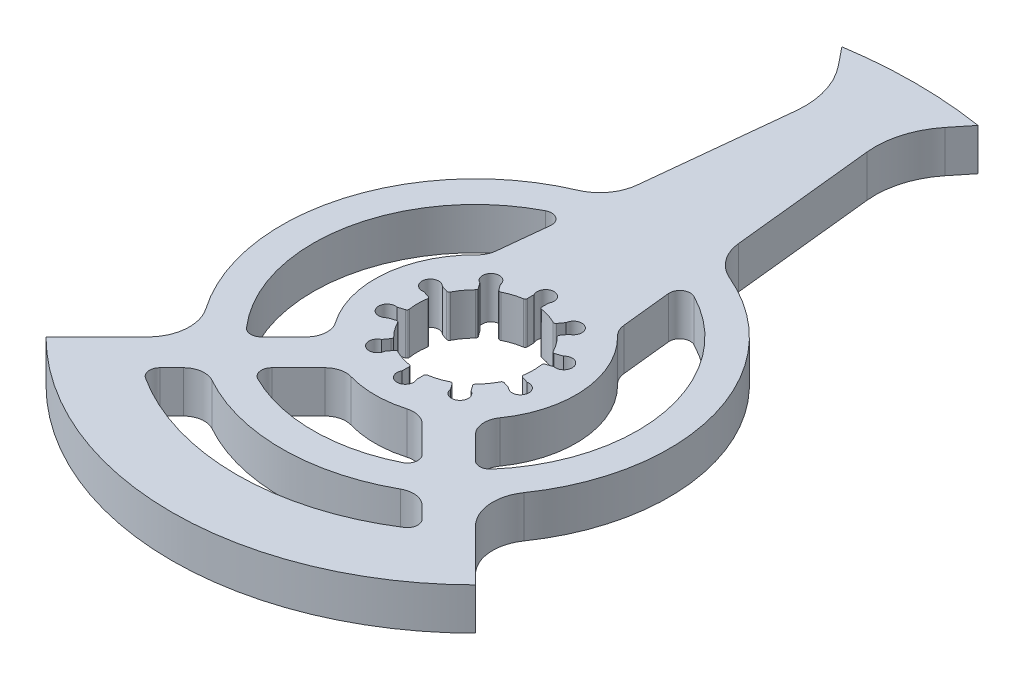
SolidWorks part; units mm, degrees
material "AISI Type A2 Tool Steel"
ref_plane "Front Plane" through (0, 0, 0) normal (0, 0, 1) x (1, 0, 0)
ref_plane "Top Plane" through (0, 0, 0) normal (0, 1, 0) x (1, 0, 0)
ref_plane "Right Plane" through (0, 0, 0) normal (1, 0, 0) x (0, 0, -1)
other "Center of Mass"
other "Bounding Box"
ref_plane "Default Plane" through (0, 2.286, 19.05) normal (0, -1, 0) x (-1, 0, 0)
sketch "Sketch1" plane through (0, 0, 0) normal (0, 1, 0) x (1, 0, 0)
  circle A0 centre (0, 0) radius 133.35 construction
  circle A1 centre (0, 0) radius 30.48
  circle A2 centre (0, 0) radius 17.4625
  dimension "D1" = 266.7
  dimension "D2" = 60.96
  dimension "D3" = 34.925
extrude "Boss-Extrude1" add sketch "Sketch1" along normal mid plane 12.7
sketch "Sketch2" plane through (0, 6.35, 0) normal (0, 1, 0) x (1, 0, 0)
  line L0 (-10.795, 107.95) -> (-19.6961, 23.2614)
  line L1 (19.6961, 23.2614) -> (10.795, 107.95)
  line L4 (0, 0) -> (0, 133.35) construction
  line L5 (-10.795, 107.95) -> (0, 107.95) construction
  line L6 (0, 107.95) -> (10.795, 107.95) construction
  line L7 (-20.6375, 131.7434) -> (0, 0) construction
  line L8 (-20.6375, 131.7434) -> (124.4119, -47.9991) construction
  line L9 (-20.6375, 131.7434) -> (-16.1956, 126.2391)
  line L10 (20.6375, 131.7434) -> (16.1956, 126.2391)
  circle A0 centre (0, 0) radius 133.35 construction
  circle A1 centre (0, 0) radius 133.35 construction
  arc A2 (-20.6375, 131.7434) -> (20.6375, 131.7434) centre (0, 0) cw
  circle A5 centre (0, 0) radius 30.48
  arc A6 (19.6961, 23.2614) -> (-19.6961, 23.2614) centre (0, 0) ccw
  arc A7 (-19.6961, 23.2614) -> (19.6961, 23.2614) centre (0, 0) ccw construction
  arc A9 (-16.1956, 126.2391) -> (-10.795, 107.95) centre (-35.6252, 110.5598) cw
  arc A10 (16.1956, 126.2391) -> (10.795, 107.95) centre (35.6252, 110.5598) ccw
  dimension "D3" = 41.275
  dimension "D4" = 25.4
  dimension "D5" = 6
  dimension "D6" = 10.795
  dimension "D1" = 30
  dimension "D2" = 0
extrude "Boss-Extrude2" add sketch "Sketch2" against normal through all
sketch "Sketch3" plane through (0, 6.35, 0) normal (0, 1, 0) x (1, 0, 0)
  line L0 (-65.1069, -65.1069) -> (-21.5526, -21.5526)
  line L1 (21.5526, -21.5526) -> (65.1069, -65.1069)
  line L2 (0, -30.48) -> (0, -92.075) construction
  line L4 (-21.5526, -21.5526) -> (0, 0) construction
  line L5 (0, 0) -> (21.5526, -21.5526) construction
  arc A0 (-65.1069, -65.1069) -> (65.1069, -65.1069) centre (0, 0) ccw
  circle A1 centre (0, 0) radius 30.48 construction
  arc A3 (-21.5526, -21.5526) -> (21.5526, -21.5526) centre (0, 0) ccw
  point P13 (0, -92.075)
  dimension "D2" = 92.075
  dimension "D1" = 90
extrude "Boss-Extrude3" add sketch "Sketch3" against normal through all
sketch "Sketch5" plane through (0, 6.35, 0) normal (0, 1, 0) x (1, 0, 0)
  line L0 (0, 17.4625) -> (0, 21.2725) construction
  line L2 (-2.2225, 17.3205) -> (2.2225, 17.3205)
  line L3 (-2.2225, 17.3205) -> (-2.2225, 20.0168)
  line L5 (2.2225, 17.3205) -> (2.2225, 20.0168)
  arc A0 (2.2225, 20.0168) -> (-2.2225, 20.0168) centre (0, 21.2725) ccw
  circle A1 centre (0, 0) radius 17.4625 construction
  circle A2 centre (0, 21.2725) radius 4.5847 construction
  dimension "D2" = 5.1054
  dimension "D4" = 9.1694
  dimension "D1" = 3.81
  dimension "D3" = 4.445
extrude "Cut-Extrude2" cut sketch "Sketch5" against normal through all
pattern_circular "CirPattern1" count 10 over 360 about axis through (0, 6.35, 0) along (0, -1, 0) of "Cut-Extrude2"
sketch "Sketch6" plane through (0, 6.35, 0) normal (0, 1, 0) x (1, 0, 0)
  circle A0 centre (0, 0) radius 17.526
  arc A1 (-11.9788, 12.7062) -> (-15.786, 7.466) centre (0, 0) ccw construction
  dimension "D1" = 0.0635
extrude "Cut-Extrude3" cut sketch "Sketch6" against normal through all
sketch "Sketch7" plane through (0, 6.35, 0) normal (0, 1, 0) x (1, 0, 0)
  line L0 (-42.454, -58.6185) -> (-11.8976, -28.062)
  line L1 (11.8976, -28.062) -> (42.454, -58.6185)
  line L3 (-21.5526, -21.5526) -> (-65.1069, -65.1069) construction
  line L4 (65.1069, -65.1069) -> (21.5526, -21.5526) construction
  line L5 (-42.454, -58.6185) -> (-50.5363, -50.5363) construction
  line L6 (42.454, -58.6185) -> (50.5363, -50.5363) construction
  arc A0 (-11.8976, -28.062) -> (11.8976, -28.062) centre (0, 0) ccw
  arc A1 (-42.454, -58.6185) -> (42.454, -58.6185) centre (0, 0) ccw
  arc A2 (-65.1069, -65.1069) -> (65.1069, -65.1069) centre (0, 0) ccw construction
  arc A4 (21.5526, -21.5526) -> (19.6961, 23.2614) centre (0, 0) ccw construction
  dimension "D1" = 19.6977
  dimension "D2" = 11.43
extrude "Cut-Extrude4" cut sketch "Sketch7" against normal through all
sketch "Sketch8" plane through (0, 6.35, 0) normal (0, 1, 0) x (1, 0, 0)
  circle A0 centre (0, 0) radius 49.2125
  circle A1 centre (0, 0) radius 58.7375
  dimension "D1" = 9.525
  dimension "D2" = 117.475
extrude "Boss-Extrude4" add sketch "Sketch8" against normal through all
sketch "Sketch11" plane through (0, 6.35, 0) normal (0, 1, 0) x (1, 0, 0)
  line L0 (-7.5441, 29.5316) -> (-5.5081, 48.9033)
  line L1 (5.5081, 48.9033) -> (7.5441, 29.5316)
  line L3 (-17.2986, 46.072) -> (-19.6961, 23.2614) construction
  line L4 (19.6961, 23.2614) -> (17.2986, 46.072) construction
  line L5 (-6.5261, 39.2174) -> (-17.8935, 40.4122) construction
  line L6 (6.5261, 39.2174) -> (17.8935, 40.4122) construction
  arc A0 (-7.5441, 29.5316) -> (7.5441, 29.5316) centre (0, 0) cw
  arc A1 (-5.5081, 48.9033) -> (5.5081, 48.9033) centre (0, 0) cw
  arc A2 (-19.6961, 23.2614) -> (-21.5526, -21.5526) centre (0, 0) ccw construction
  arc A3 (-17.2986, 46.072) -> (-34.7985, -34.7985) centre (0, 0) ccw construction
  dimension "D1" = 11.43
extrude "Cut-Extrude6" [suppressed] cut sketch "Sketch11" against normal through all
fillet "Fillet1" radius 6.35 8 edges at (-21.5526, 0, 21.5526) (21.5526, 0, 21.5526) (19.6961, 0, -23.2614) (-19.6961, 0, -23.2614) (11.8976, 0, 28.062) (-11.8976, 0, 28.062) (32.6575, 0, 48.8219) (-32.6575, 0, 48.8219)
fillet "Fillet6" radius 0.635 20 edges at (-12.0164, 0, -12.758) (-15.8469, 0, -7.4858) (-17.2204, 0, -3.2584) (-17.2204, 0, 3.2584) (-15.8469, 0, 7.4858) (-12.0164, 0, 12.758) (-8.4203, 0, 15.3707) (-2.2225, 0, 17.3845) (2.2225, 0, 17.3845) (8.4203, 0, 15.3707) (12.0164, 0, 12.758) (15.8469, 0, 7.4858) (17.2204, 0, 3.2584) (17.2204, 0, -3.2584) (15.8469, 0, -7.4858) (12.0164, 0, -12.758) (8.4203, 0, -15.3707) (2.2225, 0, -17.3845) (-2.2225, 0, -17.3845) (-8.4203, 0, -15.3707)
fillet "Fillet7" radius 3.175 8 edges at (-25.7647, 0, 41.9291) (25.7647, 0, 41.9291) (34.7985, 0, 34.7985) (-34.7985, 0, 34.7985) (-17.2986, 0, -46.072) (17.2986, 0, -46.072) (42.454, 0, 58.6185) (-42.454, 0, 58.6185)
fillet "Fillet8" radius 12.7 4 edges at (-16.2071, 0, -56.4573) (16.2071, 0, -56.4573) (41.5337, 0, 41.5337) (-41.5337, 0, 41.5337)
fillet "Fillet9" [suppressed] radius 3.175
sketch "Sketch12" plane through (0, -6.35, 0) normal (0, -1, 0) x (1, 0, 0)
  line L0 (-58.7375, 0) -> (-53.975, 0) construction
  line L1 (-53.975, 0) -> (-49.2125, 0) construction
  circle A0 centre (0, 0) radius 53.975
  arc A1 (-48.2558, 33.4883) -> (-23.0251, -54.0365) centre (0, 0) ccw construction
  arc A2 (-37.1155, 32.3157) -> (-22.4793, -43.7784) centre (0, 0) ccw construction
equation "\"Unit Measure\"= \"BoundingVolume\" / \"Thickness\"'in^2"
